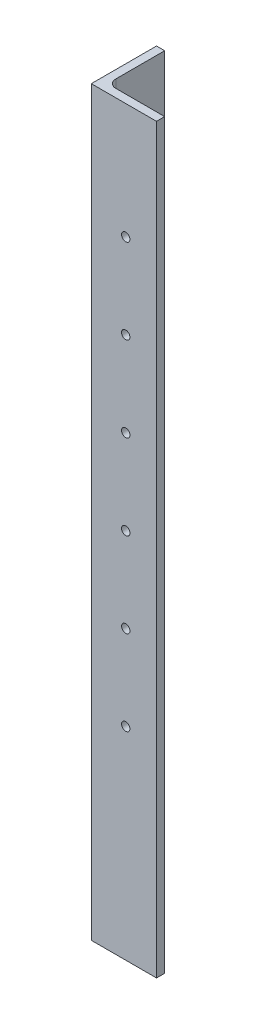
SolidWorks part; units mm, degrees
material "6061 Alloy"
ref_plane "Front Plane" through (0, 0, 0) normal (0, 0, 1) x (1, 0, 0)
ref_plane "Top Plane" through (0, 0, 0) normal (0, 1, 0) x (1, 0, 0)
ref_plane "Right Plane" through (0, 0, 0) normal (1, 0, 0) x (0, 0, -1)
sketch "Sketch2" plane through (0, 6.35, 0) normal (0, 1, 0) x (1, 0, 0)
  line L0 (-304.8, -406.4) -> (-304.8, -457.2)
  line L1 (-304.8, -457.2) -> (-254, -457.2)
  line L2 (-254, -457.2) -> (-254, -450.85)
  line L3 (-254, -450.85) -> (-298.45, -450.85)
  line L4 (-298.45, -450.85) -> (-298.45, -406.4)
  line L5 (-298.45, -406.4) -> (-304.8, -406.4)
  dimension "D1" = 6.35
  dimension "D2" = 50.8
  dimension "D3" = 50.8
extrude "Boss-Extrude1" add sketch "Sketch2" along normal offset from surface (577.85 mm away) 19.05
fillet "Fillet1" radius 6.35 1 edges at (-298.45, 295.275, 450.85)
sketch "Sketch3" plane through (0, 0, 457.2) normal (0, 0, 1) x (1, 0, 0)
  point P0 (-535.515, 347.0145)
  point P1 (-277.9825, 164.0153)
hole_wizard "F (0.257) Diameter Hole1" positions "Sketch3" profile "Sketch4" hole size "F" standard "ANSI Inch" end condition through all
sketch "Sketch4" plane through (-535.515, 347.0145, 457.2) normal (1, 0, 0) x (0, -1, 0)
  line L0 (0, 0) -> (0, 50.8)
  line L1 (0, 50.8) -> (3.2639, 50.8)
  line L2 (3.2639, 50.8) -> (3.2639, 0)
  line L5 (3.2639, 0) -> (0, 0)
  line L11 (0, -6.35) -> (0, 107.95) construction
  dimension "Thru Hole Dia." = 6.5278
  dimension "Thru Hole Depth" = 50.8
pattern_linear "LPattern1" count 6 spacing 66.04 along (0, 1, 0) of "F (0.257) Diameter Hole1"
ref_plane "Plane1" through (0, 164.0153, 0) normal (0, 1, 0) x (1, 0, 0)
ref_plane "Plane2" through (0, 0, 431.8) normal (0, 0, 1) x (1, 0, 0)
sketch "Sketch5" plane through (-304.8, 0, 0) normal (-1, 0, 0) x (0, 0, 1)
  line L0 (431.8, -27.94) -> (431.8, 27.94) construction
  line L1 (29.8147, 164.0153) -> (-29.8147, 164.0153) construction
  point P0 (431.8, 164.0153)
hole_wizard "F (0.257) Diameter Hole2" positions "Sketch5" profile "Sketch6" hole size "F" standard "ANSI Inch" end condition through all
sketch "Sketch6" plane through (-304.8, 164.0153, 431.8) normal (0, 1, 0) x (0, 0, 1)
  line L0 (0, 0) -> (0, 50.8)
  line L1 (0, 50.8) -> (3.2639, 50.8)
  line L2 (3.2639, 50.8) -> (3.2639, 0)
  line L5 (3.2639, 0) -> (0, 0)
  line L11 (0, -6.35) -> (0, 107.95) construction
  dimension "Thru Hole Dia." = 6.5278
  dimension "Thru Hole Depth" = 50.8
pattern_linear "LPattern2" count 6 spacing 66.04 along (0, 1, 0) of "F (0.257) Diameter Hole2"
